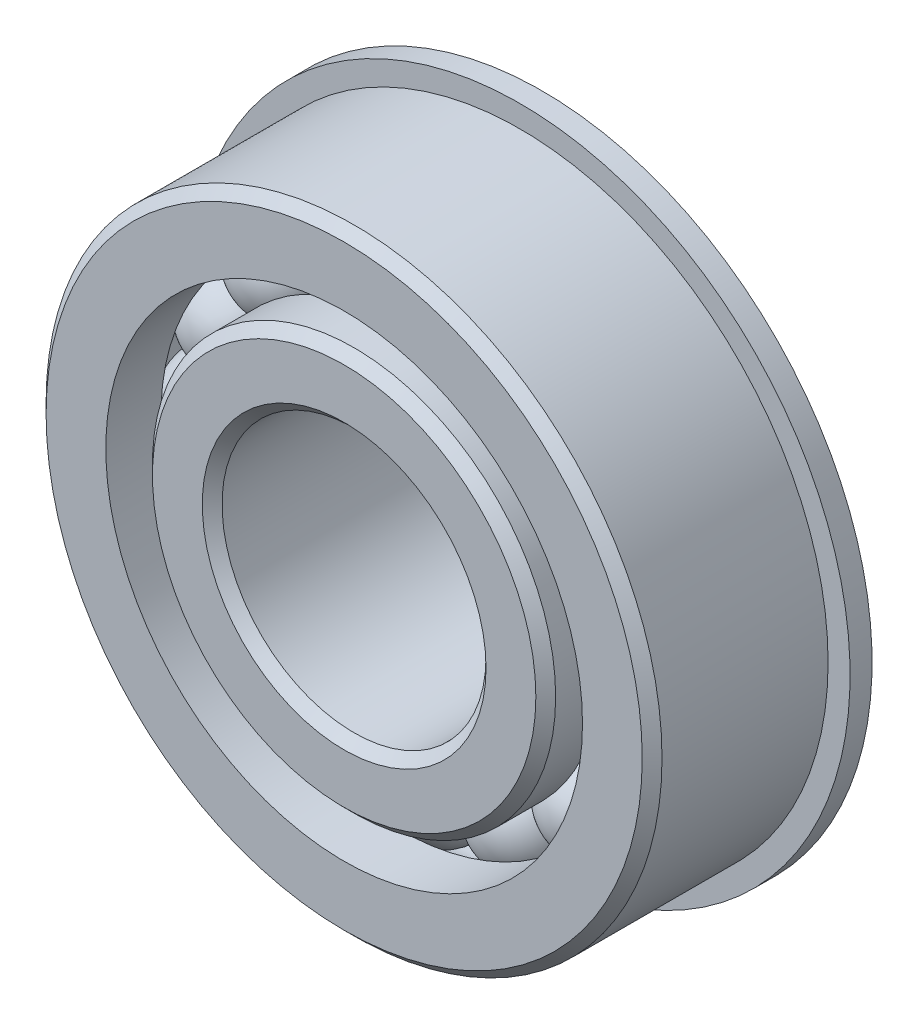
SolidWorks part; units mm, degrees
ref_plane "Front Plane" through (0, 0, 0) normal (0, 0, 1) x (1, 0, 0)
ref_plane "Top Plane" through (0, 0, 0) normal (0, 1, 0) x (1, 0, 0)
ref_plane "Right Plane" through (0, 0, 0) normal (1, 0, 0) x (0, 0, -1)
sketch "Sketch1" plane through (0, 0, 0) normal (1, 0, 0) x (0, 0, -1)
  line L0 (-7.1437, 0) -> (7.1437, 0) construction
  line L1 (0, 22.225) -> (0, -22.225) construction
  line L2 (6.4294, 22.225) -> (-6.4294, 22.225)
  line L3 (-6.4294, 22.225) -> (-7.1438, 21.5106)
  line L4 (-7.1438, 21.5106) -> (-7.1438, 17.2008)
  line L5 (-7.1438, 17.2008) -> (-3.175, 17.2008)
  line L6 (7.1438, 17.2008) -> (3.175, 17.2008)
  line L7 (7.1438, 21.5106) -> (7.1438, 17.2008)
  line L8 (6.4294, 22.225) -> (7.1438, 21.5106)
  line L9 (0, 22.225) -> (0, 15.875) construction
  line L10 (0, 15.875) -> (0, 9.525) construction
  arc A0 (-3.175, 17.2008) -> (3.175, 17.2008) centre (0, 15.875) cw
  point P14 (0, 9.525)
  dimension "Width" = 14.2875
  dimension "OD" = 44.45
  dimension "D1" = 45
  dimension "D2" = 0.7144
  dimension "D3" = 6.35
  dimension "D4" = 1.3258
revolve "Revolve1" add sketch "Sketch1" angle 360 about L0
sketch "Sketch3" plane through (0, 0, 0) normal (1, 0, 0) x (0, 0, -1)
  line L0 (-3.175, 14.5492) -> (-7.1438, 14.5492) construction
  line L1 (-7.1438, 21.5106) -> (-7.1438, 17.2008) construction
  line L2 (-6.4294, 22.225) -> (-7.1438, 21.5106) construction
  line L3 (-7.1438, 14.5492) -> (-7.1438, 10.2394) construction
  line L4 (-7.1438, 10.2394) -> (-7.1438, 13.8348)
  line L5 (-7.1438, 10.2394) -> (-6.4294, 9.525)
  line L6 (-6.4294, 9.525) -> (8.0169, 9.525)
  line L7 (-7.1438, 21.5106) -> (-7.1438, -21.5106) construction
  line L8 (8.0169, 9.525) -> (8.7312, 10.2394)
  line L10 (8.7312, 10.2394) -> (8.7312, 14.5492) construction
  line L11 (8.7312, 14.5492) -> (3.175, 14.5492) construction
  line L12 (0, 22.225) -> (0, -22.225) construction
  line L13 (6.4294, 22.225) -> (7.1438, 21.5106) construction
  line L14 (-7.1438, 13.8348) -> (-6.4294, 14.5492)
  line L15 (-6.4294, 14.5492) -> (-3.175, 14.5492)
  line L16 (3.175, 14.5492) -> (8.0169, 14.5492)
  line L17 (8.0169, 14.5492) -> (8.7312, 13.8348)
  line L18 (8.7312, 13.8348) -> (8.7312, 10.2394)
  arc A1 (3.175, 14.5492) -> (-3.175, 14.5492) centre (0, 15.875) cw
  arc A2 (3.175, 17.2008) -> (-3.175, 17.2008) centre (0, 15.875) ccw construction
  dimension "D1" = 45
  dimension "Ring Wd" = 15.875
revolve "Revolve3" add sketch "Sketch3" angle 360 about L0
sketch "Sketch4" plane through (0, 0, 0) normal (1, 0, 0) x (0, 0, -1)
  line L0 (-3.4407, 15.875) -> (3.4407, 15.875)
  arc A2 (-3.4407, 15.875) -> (3.4407, 15.875) centre (0, 15.875) cw
  arc A3 (3.175, 17.2008) -> (-3.175, 17.2008) centre (0, 15.875) ccw construction
revolve "Revolve4" add sketch "Sketch4" angle 360 about L0
ref_axis "Axis1" through (0, 0, -7.1437) along (0, 0, 1)
pattern_circular "CirPattern1" count 16 every 22.5 about axis through (0, 0, -7.1437) along (0, 0, 1) of bodies 104
sketch "Sketch5" plane through (0, 0, 0) normal (1, 0, 0) x (0, 0, -1)
  line L0 (-7.1438, 17.2008) -> (-3.175, 17.2008) construction
  line L1 (-6.7866, 17.2008) -> (-3.4407, 17.2008)
  line L2 (-6.7866, 17.2008) -> (-6.7866, 14.5492)
  line L3 (-6.7866, 14.5492) -> (-3.4407, 14.5492)
  line L4 (-3.4407, 17.2008) -> (-3.4407, 14.5492)
  line L5 (-3.175, 14.5492) -> (-7.1438, 14.5492) construction
  line L6 (7.1438, 17.2008) -> (3.175, 17.2008) construction
  line L7 (6.7866, 17.2008) -> (3.4407, 17.2008)
  line L8 (6.7866, 17.2008) -> (6.7866, 14.5492)
  line L9 (6.7866, 14.5492) -> (3.4407, 14.5492)
  line L10 (3.4407, 17.2008) -> (3.4407, 14.5492)
  line L11 (8.7312, 14.5492) -> (3.175, 14.5492) construction
  line L12 (-6.4294, 22.225) -> (-7.1438, 21.5106) construction
  point P18 (-6.7866, 21.8678)
revolve "Revolve5" [suppressed] add sketch "Sketch5" angle 360 about L0
sketch "Sketch6" plane through (0, 0, 0) normal (1, 0, 0) x (0, 0, -1)
  line L1 (7.1438, 17.2008) -> (5.5563, 17.2008)
  line L2 (7.1438, 17.2008) -> (7.1437, 23.8125)
  line L3 (7.1437, 23.8125) -> (5.5563, 23.8125)
  line L4 (5.5563, 17.2008) -> (5.5563, 23.8125)
  line L5 (7.1437, 0) -> (-7.1437, 0) construction
  dimension "Flange OD" = 47.625
  dimension "Th" = 1.5875
revolve "Revolve6" add sketch "Sketch6" angle 360 about L5
equation "\"D2@Sketch1\" = \"Width@Sketch1\"*.05"
equation "\"D3@Sketch1\" = \"Width@Sketch1\"/2.25"
equation "\"D4@Sketch1\" = (((\"OD@Sketch1\"-\"Width@Sketch1\")/2)/3.25)/3.5"
equation "\"D2@CirPattern1\" = 360/\"Balls@CirPattern1\""
